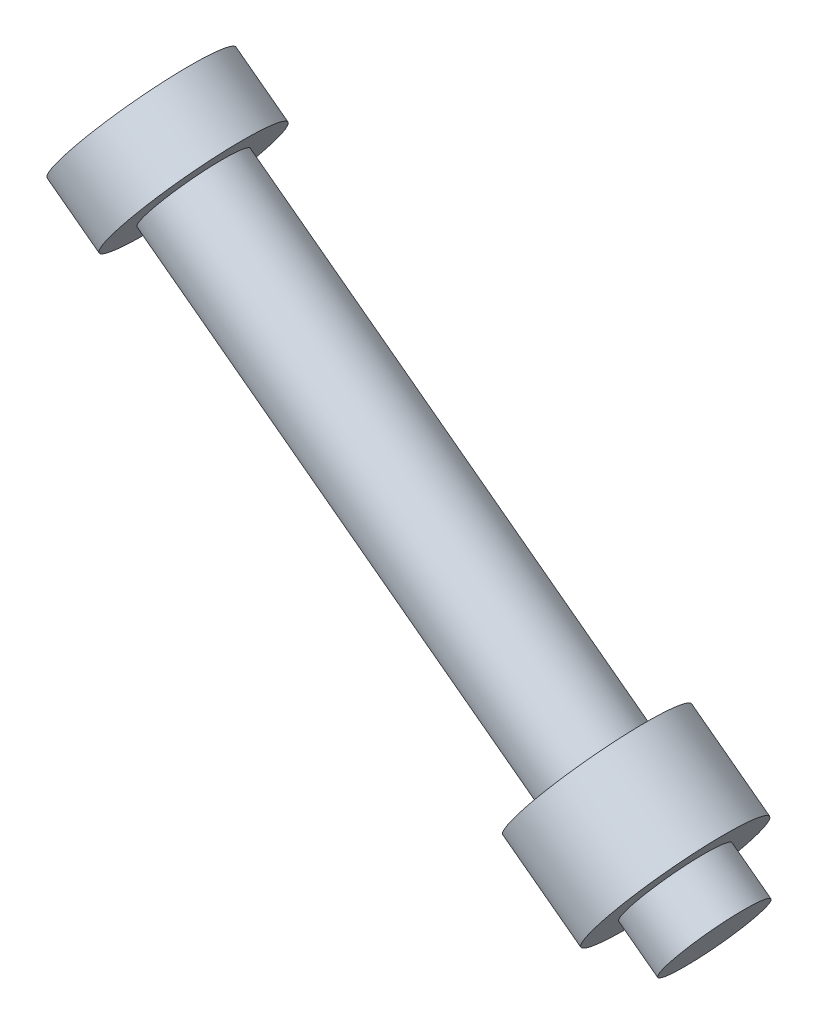
SolidWorks part; units mm, degrees
ref_plane "Alzado" through (0, 0, 0) normal (0, 0, 1) x (1, 0, 0)
ref_plane "Planta" through (0, 0, 0) normal (0, 1, 0) x (1, 0, 0)
ref_plane "Vista lateral" through (0, 0, 0) normal (1, 0, 0) x (0, 0, -1)
sketch3d "Sk_Cabeza"
  line L0 (-234.9749, 359.1356, 0) -> (-238.1775, 361.5322, 0)
  dimension "D1" = 4
sweep "Cabeza" add path "Sk_Cabeza" circular profile diameter 10 parameters "D3"=10
sketch3d "Sk_Vastago"
  line L0 (-202.9487, 335.1706, 0) -> (-234.9749, 359.1356, 0)
  dimension "D1" = 40
sweep "Vastago" add path "Sk_Vastago" circular profile diameter 6 parameters "D3"=6
sketch3d "Sk_Tuerca"
  line L0 (-205.3507, 336.968, 0) -> (-210.1546, 340.5627, 0)
  dimension "D1" = 6
sweep "Tuerca" add path "Sk_Tuerca" circular profile diameter 10 parameters "D3"=10
